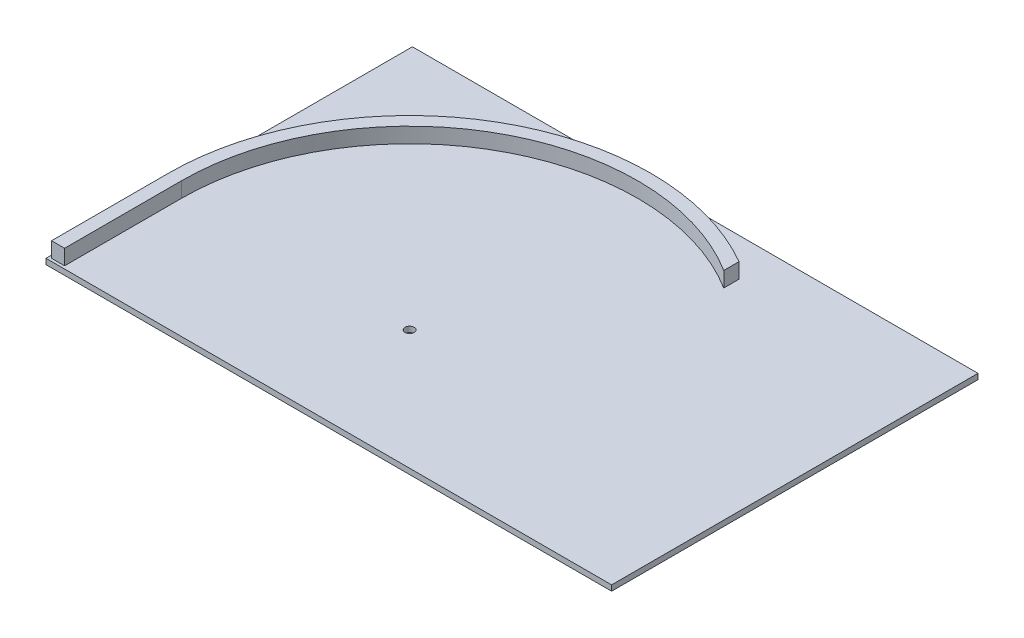
SolidWorks part; units mm, degrees
ref_plane "Front Plane" through (0, 0, 0) normal (0, 0, 1) x (1, 0, 0)
ref_plane "Top Plane" through (0, 0, 0) normal (0, 1, 0) x (1, 0, 0)
ref_plane "Right Plane" through (0, 0, 0) normal (1, 0, 0) x (0, 0, -1)
sketch "Sketch3" plane through (0, 0, 0) normal (0, 1, 0) x (1, 0, 0)
  line L1 (0, 0) -> (-839.8654, 0) construction
  line L2 (0, 0) -> (-451.1992, 260.5) construction
  line L5 (-524, 0) -> (-554, 0)
  line L6 (277.6777, 444.3772) -> (277.6777, 479.3862)
  circle A0 centre (0, 0) radius 254 construction
  arc A3 (277.6777, 444.3772) -> (-524, 0) centre (0, 0) ccw
  arc A4 (277.6777, 479.3862) -> (-554, 0) centre (0, 0) ccw
  arc A5 (293.5753, 469.8186) -> (-554, 0) centre (0, 0) ccw construction
  dimension "D1" = 524
  dimension "D2" = 30
  dimension "D4" = 122
  dimension "D5" = 508
  dimension "D3" = 30
extrude "Boss-Extrude1" add sketch "Sketch3" along normal blind 35
sketch "Sketch4" plane through (0, 0, 0) normal (0, 1, 0) x (1, 0, 0)
  line L0 (-538.2597, 554) -> (609.3192, 554) construction
  line L5 (-560.35, 566.7) -> (739.65, 566.7)
  line L6 (-560.35, 566.7) -> (-560.35, -275.4)
  line L7 (-560.35, -275.4) -> (739.65, -275.4)
  line L8 (739.65, 566.7) -> (739.65, -275.4)
  arc A0 (277.6777, 479.3862) -> (-554, 0) centre (0, 0) ccw construction
  dimension "D1" = 275.4
  dimension "D2" = 6.35
  dimension "D3" = 12.7
  dimension "D4" = 1300
extrude "Boss-Extrude2" add sketch "Sketch4" against normal blind 12.7
hole_wizard "Ø20.0mm Dowel Hole1" positions "Sketch6" profile "Sketch7" hole size "Ø20.0" standard "ANSI Metric" end condition through all
sketch "Sketch6" plane through (0, 0, 0) normal (0, 1, 0) x (1, 0, 0)
  point P0 (0, 0)
sketch "Sketch7" plane through (0, 0, 0) normal (1, 0, 0) x (0, 0, 1)
  line L0 (0, 0) -> (0, 12.7)
  line L1 (0, 12.7) -> (10.5, 12.7)
  line L2 (10.5, 12.7) -> (10.5, 0)
  line L5 (10.5, 0) -> (0, 0)
  line L11 (0, -6.35) -> (0, 107.95) construction
  dimension "Thru Hole Dia." = 21
  dimension "Thru Hole Depth" = 12.7
ref_plane "Plane1" through (0, 0, 269.05) normal (0, 0, 1) x (1, 0, 0)
sketch "Sketch8" plane through (0, 0, 0) normal (0, 0, 1) x (1, 0, 0)
  line L1 (-554, 35) -> (-524, 35)
  line L2 (-554, 35) -> (-554, 0)
  line L3 (-554, 0) -> (-524, 0)
  line L4 (-524, 35) -> (-524, 0)
extrude "Boss-Extrude3" add sketch "Sketch8" along normal up to surface (269.05 mm away) up to plane "Plane1"
